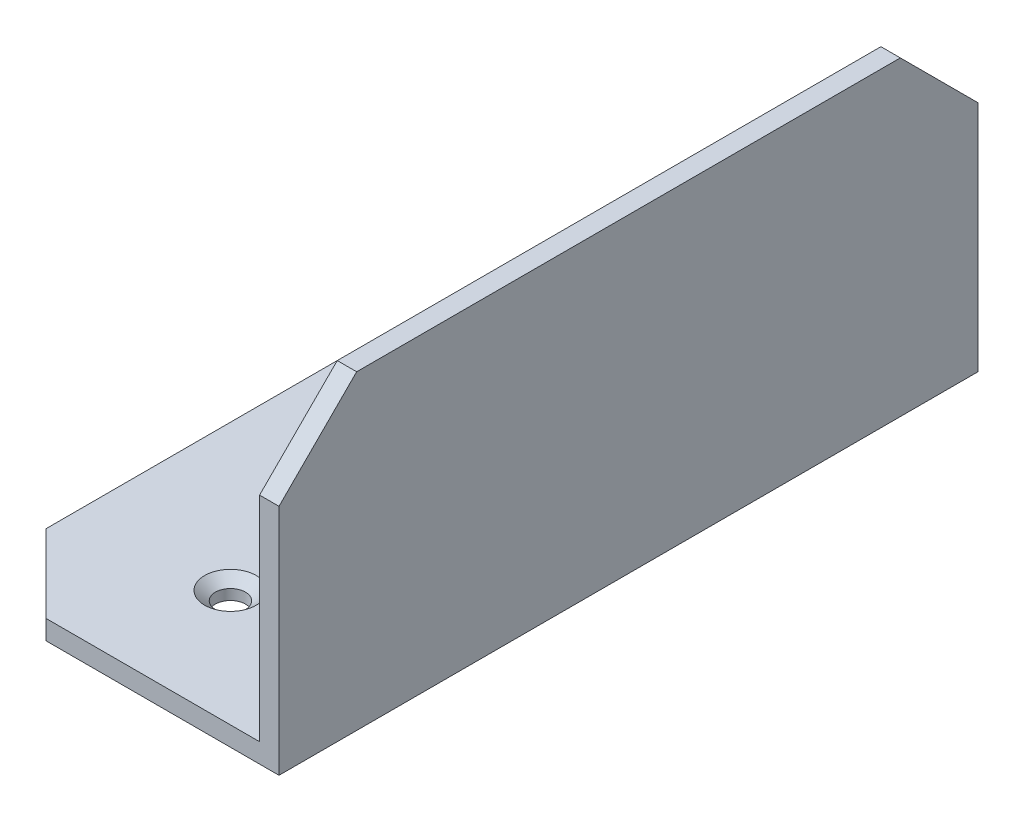
SolidWorks part; units mm, degrees
material "6063-T5"
ref_plane "Front Plane" through (0, 0, 0) normal (0, 0, 1) x (1, 0, 0)
ref_plane "Top Plane" through (0, 0, 0) normal (0, 1, 0) x (1, 0, 0)
ref_plane "Right Plane" through (0, 0, 0) normal (1, 0, 0) x (0, 0, -1)
sketch "Sketch2" plane through (0, 0, 0) normal (0, 0, 1) x (1, 0, 0)
  line L0 (0, 0) -> (0, 50.8)
  line L1 (0, 0) -> (-50.8, 0)
  line L2 (-3.175, 3.175) -> (-3.175, 50.8)
  line L3 (-3.175, 3.175) -> (-50.8, 3.175)
  line L4 (0, 50.8) -> (-3.175, 50.8)
  line L5 (-50.8, 0) -> (-50.8, 3.175)
  dimension "D1" = 50.8
  dimension "D2" = 50.8
  dimension "D3" = 3.175
extrude "Boss-Extrude1" add sketch "Sketch2" against normal blind 114.3
chamfer "Chamfer1" distance 12.7 angle 45 4 edges at (-50.8, 1.5875, -114.3) (-1.5875, 50.8, -114.3) (-1.5875, 50.8, 0) (-50.8, 1.5875, 0)
hole_wizard "CSK for #8 Flat Head Machine Screw (100)1" positions "Sketch3" profile "Sketch4" countersink size "#8" standard "ANSI Inch" end condition through all
sketch "Sketch3" plane through (0, 3.175, 0) normal (0, 1, 0) x (1, 0, 0)
  line L0 (-50.8, 57.15) -> (-3.175, 57.15) construction
  line L1 (-50.8, 101.6) -> (-50.8, 12.7) construction
  line L2 (-3.175, 114.3) -> (-3.175, 0) construction
  line L4 (-26.9875, 57.15) -> (-26.9875, 0) construction
  line L5 (-3.175, 0) -> (-38.1, 0) construction
  point P26 (-26.9875, 19.05)
  point P27 (-26.9875, 57.15)
  point P29 (-26.9875, 139.7)
  point P37 (-26.9875, 95.25)
  dimension "D1" = 38.1
sketch "Sketch4" plane through (-26.9875, 3.175, -95.25) normal (1, 0, 0) x (0, 0, 1)
  line L0 (0, 0) -> (0, 3.175)
  line L1 (0, 3.175) -> (2.4574, 3.175)
  line L2 (2.4574, 3.175) -> (2.4574, 1.4759)
  line L3 (2.4574, 1.4759) -> (4.2164, 0)
  line L5 (4.2164, 0) -> (0, 0)
  line L6 (-2.4574, 1.4759) -> (-4.2164, 0) construction
  line L11 (0, -6.35) -> (0, 107.95) construction
  dimension "Thru Hole Dia." = 4.9149
  dimension "Thru Hole Depth" = 3.175
  dimension "Near C'Sink Dia." = 8.4328
  dimension "Near C'Sink Angle" = 100
equation "\"D2@Sketch2\"=\"D1@Sketch2\""
